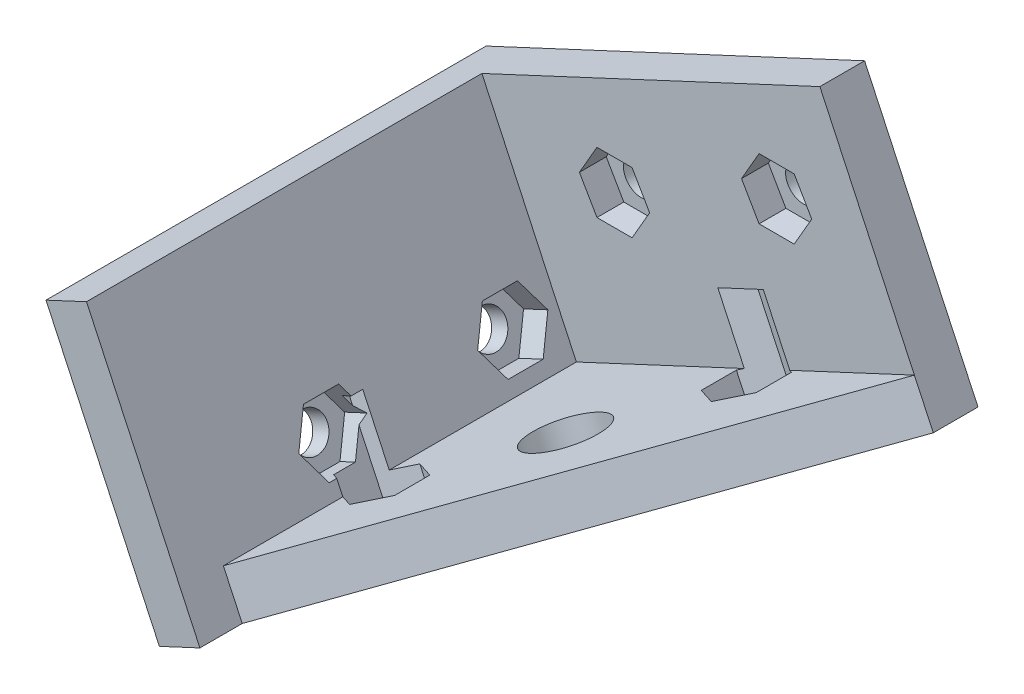
SolidWorks part; units mm, degrees
material "ABS"
ref_plane "Front Plane" through (0, 0, 0) normal (0, 0, 1) x (1, 0, 0)
ref_plane "Top Plane" through (0, 0, 0) normal (0, 1, 0) x (1, 0, 0)
ref_plane "Right Plane" through (0, 0, 0) normal (1, 0, 0) x (0, 0, -1)
sketch "Sketch1" plane through (0, 0, 0) normal (0, 0, 1) x (1, 0, 0)
  line L0 (-27.1677, -320.4736) -> (-39.8463, -293.2844)
  line L2 (-39.8463, -293.2844) -> (2.4783, -273.5481)
  line L3 (2.4783, -273.5481) -> (15.1568, -300.7373)
  line L5 (15.1568, -300.7373) -> (-27.1677, -320.4736)
  line L7 (-6.2846, -286.8374) -> (-4.3216, -290.2374)
  line L8 (-4.3216, -290.2374) -> (-0.3956, -290.2374)
  line L9 (-0.3956, -290.2374) -> (1.5674, -286.8374)
  line L10 (1.5674, -286.8374) -> (-0.3956, -283.4374)
  line L11 (-0.3956, -283.4374) -> (-4.3216, -283.4374)
  line L12 (-4.3216, -283.4374) -> (-6.2846, -286.8374)
  line L13 (-24.4107, -295.2897) -> (-22.4477, -298.6897)
  line L14 (-22.4477, -298.6897) -> (-18.5218, -298.6897)
  line L15 (-18.5218, -298.6897) -> (-16.5588, -295.2897)
  line L16 (-16.5588, -295.2897) -> (-18.5218, -291.8897)
  line L17 (-18.5218, -291.8897) -> (-22.4477, -291.8897)
  line L18 (-22.4477, -291.8897) -> (-24.4107, -295.2897)
  circle A1 centre (-2.3586, -286.8374) radius 2
  circle A2 centre (-20.4847, -295.2897) radius 2
  circle A4 centre (-2.3586, -286.8374) radius 3.4 construction
  circle A5 centre (-20.4847, -295.2897) radius 3.4 construction
  dimension "D3" = 6.8
  dimension "D4" = 6.8
extrude "Boss-Extrude1" add sketch "Sketch1" along normal blind 2 contours L5 L3 L2 L0 L18 L17 L16 L15 L14 L13 L12 L11 L10 L9 L8 L7 | L11 L12 L7 L8 L9 L10 A1 | L17 L18 L13 L14 L15 L16 A2 region at (-12.4007, -297.3715, 0) region at (-5.2131, -285.1893, 0) region at (-23.3393, -293.6417, 0)
extrude "Boss-Extrude2" add sketch "Sketch1<3>" along normal blind 3 from surface contours L5 L3 L2 L0 L18 L17 L16 L15 L14 L13 L12 L11 L10 L9 L8 L7 region at (-12.4007, -297.3715, 0) starting at face at (-12.3447, -297.0109, 2)
sketch "Sketch1<3>" plane through (0, 0, 0) normal (0, 0, 1) x (1, 0, 0) same geometry as "Sketch1"
sketch "Sketch3" plane through (117.8962, -252.8292, 0) normal (-0.4226, 0.9063, 0) x (0.9063, 0.4226, 0)
  line L0 (-113.3603, 0) -> (-113.3603, -5)
  line L1 (-113.3603, -5) -> (-160.0603, -49.2058)
  line L2 (-160.0603, 0) -> (-160.0603, -393.4) construction
  line L3 (-160.0603, -49.2058) -> (-160.0603, -5)
  line L5 (-149.3537, -26.5568) -> (-152.7537, -24.5938)
  line L6 (-152.7537, -24.5938) -> (-156.1537, -26.5568)
  line L7 (-156.1537, -26.5568) -> (-156.1537, -30.4828)
  line L8 (-156.1537, -30.4828) -> (-152.7537, -32.4458)
  line L9 (-152.7537, -32.4458) -> (-149.3537, -30.4828)
  line L10 (-149.3537, -30.4828) -> (-149.3537, -26.5568)
  line L11 (-131.5405, -3.3806) -> (-134.9405, -5.3436)
  line L12 (-134.9405, -5.3436) -> (-134.9405, -9.2696)
  line L13 (-134.9405, -9.2696) -> (-131.5405, -11.2326)
  line L14 (-131.5405, -11.2326) -> (-128.1405, -9.2696)
  line L15 (-128.1405, -9.2696) -> (-128.1405, -5.3436)
  line L16 (-128.1405, -5.3436) -> (-131.5405, -3.3806)
  line L17 (-113.3603, 0) -> (-160.0603, 0)
  line L18 (-160.0603, 0) -> (-160.0603, -5)
  circle A0 centre (-152.7537, -28.5198) radius 2 construction
  circle A1 centre (-131.5405, -7.3066) radius 2
  circle A2 centre (-152.7537, -28.5198) radius 2
  circle A3 centre (-152.7537, -28.5198) radius 3.4 construction
  circle A4 centre (-131.5405, -7.3066) radius 3.4 construction
  dimension "D1" = 10
  dimension "D2" = 4
  dimension "D3" = 4
  dimension "D4" = 6.8
  dimension "D5" = 6.8
extrude "Boss-Extrude3" add sketch "Sketch3" along normal blind 2 contours L17 L18 L3 L1 L0 L10 L9 L8 L7 L6 L5 L16 L15 L14 L13 L12 L11 | L15 L16 L11 L12 L13 L14 | L9 L10 L5 L6 L7 L8 region at (-11.8139, -313.314, 16.464) region at (-17.5584, -315.9927, 28.5198) region at (0.1737, -307.7241, 4.4521)
extrude "Boss-Extrude4" add sketch "Sketch3<4>" along normal blind 3 from surface contours L17 L18 L3 L1 L0 L10 L9 L8 L7 L6 L5 L16 L15 L14 L13 L12 L11 region at (-11.8139, -313.314, 16.464) starting at face at (-13.9048, -312.0822, 19.7353)
sketch "Sketch3<4>" plane through (117.8962, -252.8292, 0) normal (-0.4226, 0.9063, 0) x (0.9063, 0.4226, 0) same geometry as "Sketch3"
sketch "Sketch4" plane through (-145.0639, -67.6444, 0) normal (0.9063, 0.4226, 0) x (0, 0, -1)
  line L0 (-49.2058, -278.9662) -> (-49.2058, -248.9662)
  line L1 (-49.2058, -248.9662) -> (-5, -248.9662)
  line L2 (-5, -248.9662) -> (-5, -278.9662)
  line L3 (-5, -278.9662) -> (-49.2058, -278.9662)
  line L4 (-5, -248.9662) -> (0, -248.9662) construction
  line L6 (-33.926, -268.9662) -> (-31.963, -272.3662)
  line L7 (-31.963, -272.3662) -> (-28.037, -272.3662)
  line L8 (-28.037, -272.3662) -> (-26.074, -268.9662)
  line L9 (-26.074, -268.9662) -> (-28.037, -265.5662)
  line L10 (-28.037, -265.5662) -> (-31.963, -265.5662)
  line L11 (-31.963, -265.5662) -> (-33.926, -268.9662)
  line L12 (-13.926, -268.9662) -> (-11.963, -272.3662)
  line L13 (-11.963, -272.3662) -> (-8.037, -272.3662)
  line L14 (-8.037, -272.3662) -> (-6.074, -268.9662)
  line L15 (-6.074, -268.9662) -> (-8.037, -265.5662)
  line L16 (-8.037, -265.5662) -> (-11.963, -265.5662)
  line L17 (-11.963, -265.5662) -> (-13.926, -268.9662)
  circle A0 centre (-10, -268.9662) radius 2
  circle A1 centre (-30, -268.9662) radius 2
  circle A2 centre (-30, -268.9662) radius 3.4 construction
  circle A3 centre (-10, -268.9662) radius 3.4 construction
  point P14 (-27.0555, -267.2662)
  circle M11 centre (-30, -268.9662) radius 2
  circle M12 centre (-10, -268.9662) radius 2
  line M18 (-393.4, -278.9662) -> (0, -278.9662)
  dimension "D3" = 4
  dimension "D4" = 4
  dimension "D1" = 6.8
  dimension "D2" = 6.8
extrude "Boss-Extrude5" add sketch "Sketch4" along normal blind 2 contours L2 L1 L0 L17 L16 L15 L14 L13 L12 L11 L10 L9 L8 L7 L6 M18 | L10 L11 L6 L7 L8 L9 M11 | L16 L17 L12 L13 L14 L15 M12 region at (-33.6428, -306.5877, 27.5594) region at (-32.0904, -309.9169, 32.8545) region at (-32.0904, -309.9169, 12.8545)
extrude "Boss-Extrude6" add sketch "Sketch4<4>" along normal blind 3 from surface contours L2 L1 L0 L17 L16 L15 L14 L13 L12 L11 L10 L9 L8 L7 L6 M18 region at (-33.6428, -306.5877, 27.5594) starting at face at (-30.2857, -309.0548, 33.8395)
sketch "Sketch4<4>" plane through (-145.0639, -67.6444, 0) normal (0.9063, 0.4226, 0) x (0, 0, -1) same geometry as "Sketch4"
extrude "Cut-Extrude1" cut sketch "Sketch3<5>" along normal blind 10 from surface contours L15 L16 L11 L12 L13 L14 | L9 L10 L5 L6 L7 L8 region at (-17.5584, -315.9927, 28.5198) region at (0.1737, -307.7241, 4.4521) starting at face at (-3.9779, -307.4532, 7.3066)
sketch "Sketch3<5>" plane through (117.8962, -252.8292, 0) normal (-0.4226, 0.9063, 0) x (0.9063, 0.4226, 0) same geometry as "Sketch3"
sketch "Sketch5" plane through (117.8962, -252.8292, 0) normal (0.4226, -0.9063, 0) x (0.9063, 0.4226, 0)
  line L0 (-131.5405, 7.3066) -> (-152.7537, 28.5198) construction
  circle A0 centre (-142.1471, 17.9132) radius 4
  dimension "D1" = 8
extrude "Cut-Extrude2" cut sketch "Sketch5" against normal blind 10
